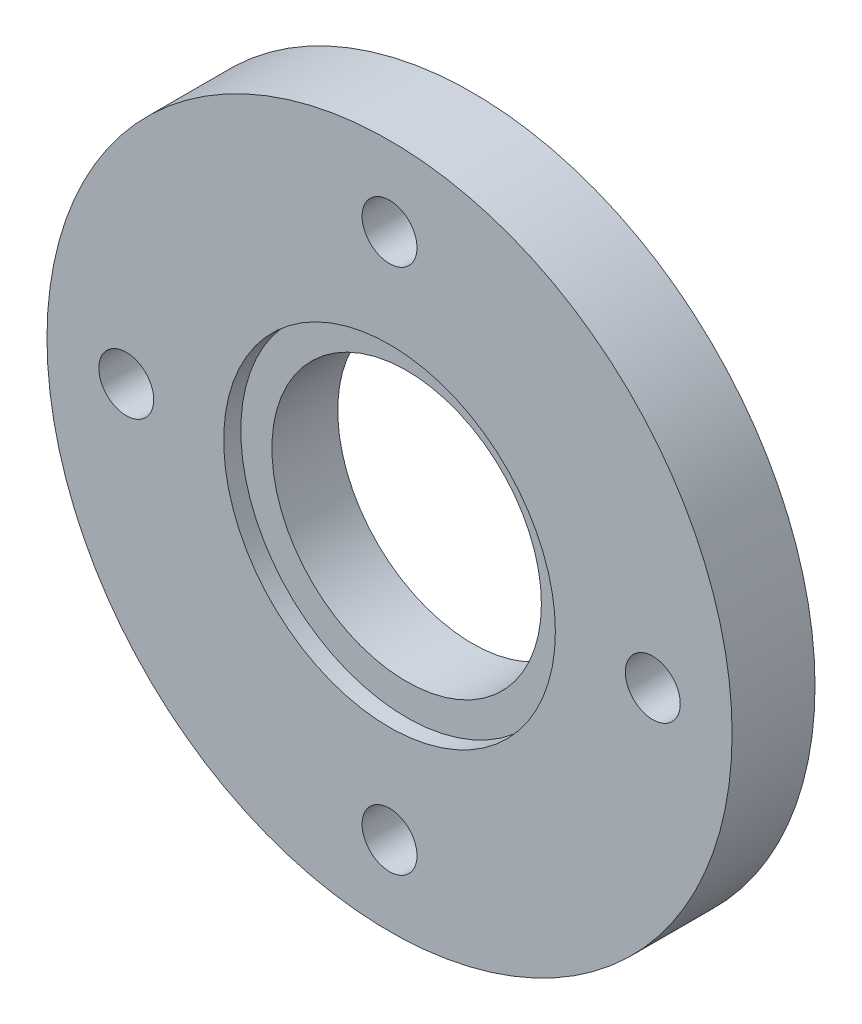
SolidWorks part; units mm, degrees
other "Markup1"
sketch "Sketch6" plane through (33.05, -33.05, -8) normal (0.0959, -0.0026, -0.9954) x (-0.8845, 0.4584, -0.0865)
other "Markup2"
sketch "Sketch7" plane through (33.05, -33.05, -8) normal (0.0959, -0.0026, -0.9954) x (-0.8845, 0.4584, -0.0865)
ref_plane "Front Plane" through (0, 0, 0) normal (0, 0, 1) x (1, 0, 0)
ref_plane "Top Plane" through (0, 0, 0) normal (0, 1, 0) x (1, 0, 0)
ref_plane "Right Plane" through (0, 0, 0) normal (1, 0, 0) x (0, 0, -1)
sketch "Sketch1" plane through (0, 0, 0) normal (0, 0, 1) x (1, 0, 0)
  circle A0 centre (0, 0) radius 13
  circle A1 centre (0, 0) radius 16 construction
  circle A3 centre (0, 0) radius 33.05
  circle A4 centre (0, 0) radius 25.4 construction
  circle A8 centre (0, 0) radius 16
  circle A12 centre (0, 0) radius 33.05
  point P21 (0, 0)
  point P70 (0, 0)
  dimension "D1" = 26
  dimension "D2" = 32
  dimension "D3" = 7.65
  dimension "D5" = 50.8
extrude "Boss-Extrude1" add sketch "Sketch1" against normal blind 8 contours A8 A0 | A8 region at (-32.1152, 0, 0) region at (-15.5475, 0, 0)
extrude "Cut-Extrude1" cut sketch "Sketch1<10>" against normal blind 1.65 contours A8 A0 region at (-15.5475, 0, 0)
sketch "Sketch1<10>" plane through (0, 0, 0) normal (0, 0, 1) x (1, 0, 0) same geometry as "Sketch1"
sketch "Sketch8" plane through (0, 0, -8) normal (0, 0, -1) x (-1, 0, 0)
  line L1 (2.4826, 21.1) -> (4.9652, 25.4)
  line L2 (4.9652, 25.4) -> (2.4826, 29.7)
  line L3 (2.4826, 29.7) -> (-2.4826, 29.7)
  line L4 (-2.4826, 29.7) -> (-4.9652, 25.4)
  line L5 (-4.9652, 25.4) -> (-2.4826, 21.1)
  line L6 (-2.4826, 21.1) -> (2.4826, 21.1)
  circle A0 centre (-59.8961, -78.4521) radius 27.9 construction
  circle A1 centre (0, 25.4) radius 4.3 construction
  circle A2 centre (0, 0) radius 25.4 construction
  circle B0 centre (-59.8961, -103.8521) radius 2.5
  circle B1 centre (-77.8566, -96.4126) radius 2.5
  circle B2 centre (-85.2961, -78.4521) radius 2.5
  circle B3 centre (-77.8566, -60.4916) radius 2.5
  circle B4 centre (-59.8961, -53.0521) radius 2.5
  circle B5 centre (-41.9356, -60.4916) radius 2.5
  circle B6 centre (-34.4961, -78.4521) radius 2.5
  circle B7 centre (-41.9356, -96.4126) radius 2.5
  dimension "D1" = 8.6
sketch_block_instance "bearing_house_holes-1"
sketch_block "bearing_house_holes"
extrude "Cut-Extrude2" cut sketch "Sketch8" against normal blind 4.1
pattern_circular "CirPattern1" count 4 every 90 about axis through (0, 0, -8) along (0, 0, 1) of "Cut-Extrude2" reverse direction yes
sketch "Sketch9" plane through (0, 0, -8) normal (0, 0, -1) x (-1, 0, 0)
  circle A0 centre (0, 25.4) radius 2.65
  circle A1 centre (0, 0) radius 25.4 construction
  dimension "D1" = 5.3
extrude "Cut-Extrude3" cut sketch "Sketch9" against normal blind 8 contours A0
pattern_circular "CirPattern2" count 4 every 90 about axis through (0, 0, -8) along (0, 0, 1) of "Cut-Extrude3"
